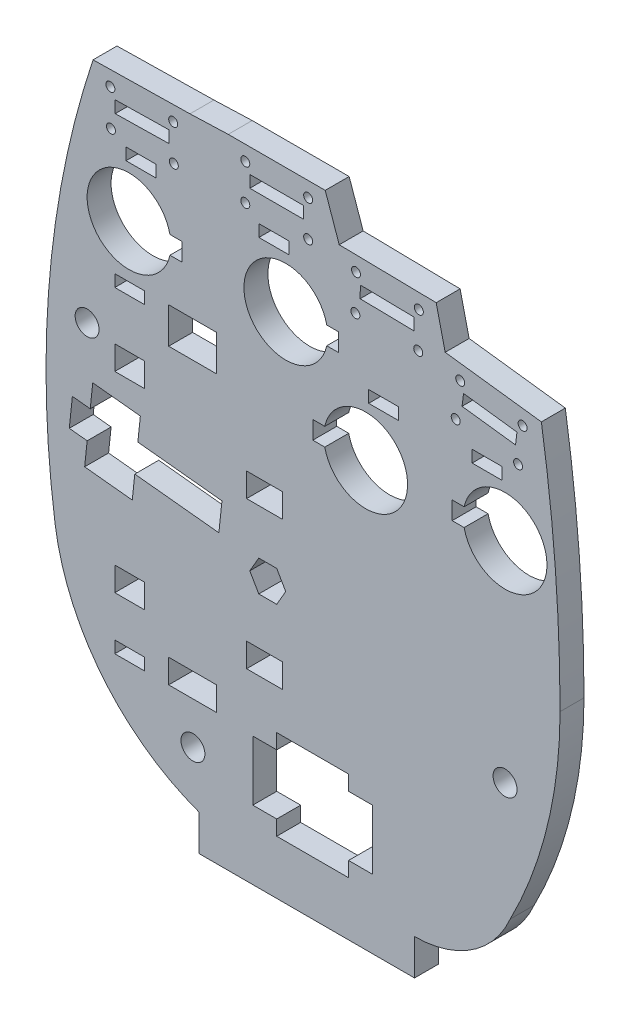
SolidWorks part; units mm, degrees
ref_plane "Front Plane" through (0, 0, 0) normal (0, 0, 1) x (1, 0, 0)
ref_plane "Top Plane" through (0, 0, 0) normal (0, 1, 0) x (1, 0, 0)
ref_plane "Right Plane" through (0, 0, 0) normal (1, 0, 0) x (0, 0, -1)
sketch "Sketch1" plane through (0, 0, 0) normal (0, 0, 1) x (1, 0, 0)
  line L0 (-4.5, 78.51) -> (-4.5, 76.51)
  line L1 (4.5, 78.51) -> (-4.5, 78.51)
  line L2 (-12.9786, -18) -> (-12.9786, -24)
  line L3 (-9.666, 24.0723) -> (-9.153, 28.9531)
  line L4 (-4.5, 76.51) -> (4.5, 76.51)
  line L5 (4.5, 76.51) -> (4.5, 78.51)
  line L6 (-34.6568, 26.6989) -> (-34.1438, 31.5798)
  line L7 (10.3588, 63.1512) -> (10.3588, 60.1512)
  line L8 (-8.1, 82.51) -> (8.1, 82.51)
  line L9 (8.3588, 63.1512) -> (10.3588, 63.1512)
  line L10 (10.4412, 75.8064) -> (26.6388, 75.5236)
  line L11 (32.6473, 57.3216) -> (37.6473, 57.3216)
  line L12 (0, 0) -> (-22.59, 0) construction
  line L13 (10.3588, 60.1512) -> (8.3588, 60.1512)
  line L14 (-17.8416, 63.1512) -> (-15.8416, 63.1512)
  line L15 (-15.8416, 63.1512) -> (-15.8416, 60.1512)
  line L16 (-15.8416, 60.1512) -> (-17.8416, 60.1512)
  line L17 (32.6473, 55.3216) -> (37.6473, 55.3216)
  line L18 (37.6473, 55.3216) -> (37.6473, 57.3216)
  line L19 (32.6473, 57.3216) -> (32.6473, 55.3216)
  line L20 (-27.0195, 78.062) -> (-18.0208, 78.2192)
  line L21 (-27.0195, 78.062) -> (-26.9845, 76.0623)
  line L22 (-10.0543, 52.8756) -> (-18.0543, 52.8756)
  line L23 (-9.153, 28.9531) -> (-23.2041, 30.43)
  line L24 (-26.9845, 76.0623) -> (-17.9858, 76.2195)
  line L25 (-24.1352, 21.571) -> (-32.0914, 22.4072)
  line L26 (-32.0914, 22.4072) -> (-31.6733, 26.3853)
  line L27 (-23.7171, 25.5491) -> (-9.666, 24.0723)
  line L28 (-17.9858, 76.2195) -> (-18.0208, 78.2192)
  line L29 (15.3631, 57.3216) -> (20.3631, 57.3216)
  line L30 (15.3631, 55.3216) -> (20.3631, 55.3216)
  line L31 (-12.9786, -24) -> (23.0214, -24)
  line L32 (20.3631, 55.3216) -> (20.3631, 57.3216)
  line L33 (23.0214, -24) -> (23.0214, -18)
  line L34 (15.3631, 57.3216) -> (15.3631, 55.3216)
  line L35 (-2.9786, 72.1512) -> (2.0214, 72.1512)
  line L36 (13.9709, 71.7441) -> (13.936, 69.7444)
  line L37 (13.936, 69.7444) -> (22.9346, 69.5874)
  line L38 (8.0257, 48.3216) -> (6.0257, 48.3216)
  line L39 (-2.9786, 70.1512) -> (2.0214, 70.1512)
  line L40 (22.9695, 71.5871) -> (13.9709, 71.7441)
  line L41 (6.0257, 48.3216) -> (6.0257, 45.3216)
  line L42 (22.9346, 69.5874) -> (22.9695, 71.5871)
  line L43 (-22.59, 0) -> (-22.59, 82.14) construction
  line L44 (2.0214, 70.1512) -> (2.0214, 72.1512)
  line L45 (18.54, 75.665) -> (18.5934, 78.7251) construction
  line L46 (-2.9786, 72.1512) -> (-2.9786, 70.1512)
  line L47 (40.1436, 63.5476) -> (31.2139, 64.6755)
  line L48 (6.0257, 45.3216) -> (8.0257, 45.3216)
  line L49 (29.3099, 45.3216) -> (31.3099, 45.3216)
  line L50 (29.3099, 48.3216) -> (29.3099, 45.3216)
  line L51 (31.3099, 48.3216) -> (29.3099, 48.3216)
  line L52 (-22.786, 34.408) -> (-30.7422, 35.2443)
  line L53 (31.2139, 64.6755) -> (30.9632, 62.6912)
  line L54 (-25.179, 72.1512) -> (-20.179, 72.1512)
  line L55 (-30.6888, 81.9985) -> (-14.4912, 82.2815)
  line L56 (44.2162, 67.065) -> (28.1438, 69.095)
  line L57 (-25.179, 70.1512) -> (-20.179, 70.1512)
  line L58 (30.9632, 62.6912) -> (39.893, 61.5633)
  line L59 (-20.179, 70.1512) -> (-20.179, 72.1512)
  line L60 (-25.179, 72.1512) -> (-25.179, 70.1512)
  line L61 (39.893, 61.5633) -> (40.1436, 63.5476)
  line L62 (-34.6568, 26.6989) -> (-31.6733, 26.3853)
  line L63 (-4, -2.5) -> (0, -2.5)
  line L64 (12, 0) -> (0, 0)
  line L65 (12, 0) -> (12, -2.5)
  line L66 (12, -15) -> (0, -15)
  line L67 (-30.7422, 35.2443) -> (-31.1603, 31.2662)
  line L68 (-23.2041, 30.43) -> (-22.786, 34.408)
  line L69 (-34.1438, 31.5798) -> (-31.1603, 31.2662)
  line L70 (-24.1352, 21.571) -> (-23.7171, 25.5491)
  line L71 (16, -7.5) -> (38.9913, -7.5) construction
  line L72 (0, -15) -> (0, -12.5)
  line L73 (-4, -12.5) -> (-4, -2.5)
  line L74 (-4, -12.5) -> (0, -12.5)
  line L75 (0, -2.5) -> (0, 0)
  line L76 (0, 0) -> (0, 82.51) construction
  line L77 (-22.0543, 52.8756) -> (-27.0543, 52.8756)
  line L78 (-10.0543, -2.1244) -> (-18.0543, -2.1244)
  line L79 (-22.0543, -2.1244) -> (-27.0543, -2.1244)
  line L80 (0, 0) -> (18.54, 0) construction
  line L81 (16, -12.5) -> (12, -12.5)
  line L82 (16, -12.5) -> (16, -2.5)
  line L83 (16, -2.5) -> (12, -2.5)
  line L84 (12, -12.5) -> (12, -15)
  line L85 (-9.4095, 26.5127) -> (6.8756, 24.8011) construction
  line L86 (0, 23.7547) -> (-3, 23.7547)
  line L87 (-3, 23.7547) -> (-4.5, 21.1566)
  line L88 (-4.5, 21.1566) -> (-3, 18.5585)
  line L89 (18.54, 0) -> (18.54, 75.665) construction
  line L90 (0, 0) -> (36.18, 0) construction
  line L91 (36.18, 0) -> (36.18, 68.08) construction
  line L92 (28.1438, 69.095) -> (26.6388, 75.5236)
  line L93 (10.4412, 75.8064) -> (8.1, 82.51)
  line L94 (-8.1, 82.51) -> (-14.4912, 82.2815)
  line L95 (-34.6568, 26.6989) -> (47.3354, 26.6989) construction
  line L96 (35.6788, 64.1115) -> (36.18, 68.08) construction
  line L97 (-3, 18.5585) -> (0, 18.5585)
  line L98 (0, 18.5585) -> (1.5, 21.1566)
  line L99 (1.5, 21.1566) -> (0, 23.7547)
  line L100 (0, 18.5585) -> (-3, 23.7547) construction
  line L101 (0, 23.7547) -> (-3, 18.5585) construction
  line L102 (38.1473, 11.8216) -> (-37.0527, 11.8216) construction
  line L103 (-27.7956, 79.5486) -> (-30.6451, 79.4989) construction
  line L104 (0.9634, 10.717) -> (0.9634, 6.717)
  line L105 (0.9634, 6.717) -> (-5.0366, 6.717)
  line L106 (-5.0366, 6.717) -> (-5.0366, 10.717)
  line L107 (-5.0366, 10.717) -> (0.9634, 10.717)
  line L108 (-5.0366, 31.3356) -> (0.9634, 31.3356)
  line L109 (-5.0366, 35.3356) -> (-5.0366, 31.3356)
  line L110 (0.9634, 35.3356) -> (-5.0366, 35.3356)
  line L111 (0.9634, 31.3356) -> (0.9634, 35.3356)
  line L112 (-30.6451, 79.4989) -> (-30.6888, 81.9985) construction
  line L113 (-17.2971, 79.732) -> (-14.4475, 79.7819) construction
  line L114 (-14.4475, 79.7819) -> (-14.4912, 82.2815) construction
  line L115 (-22.5201, 78.1406) -> (-22.59, 82.14) construction
  line L116 (5.25, 80.01) -> (8.1, 80.01) construction
  line L117 (8.1, 80.01) -> (8.1, 82.51) construction
  line L118 (-5.25, 80.01) -> (-8.1, 80.01) construction
  line L119 (-22.0543, -0.1244) -> (-27.0543, -0.1244)
  line L120 (-8.1, 80.01) -> (-8.1, 82.51) construction
  line L121 (-10.0543, 1.8756) -> (-10.0543, -2.1244)
  line L122 (30.6581, 66.2576) -> (27.8306, 66.6147) construction
  line L123 (-10.0543, 52.8756) -> (-10.0543, 46.8756)
  line L124 (-10.0543, 1.8756) -> (-18.0543, 1.8756)
  line L125 (-18.0543, 1.8756) -> (-18.0543, -2.1244)
  line L126 (27.8306, 66.6147) -> (28.1438, 69.095) construction
  line L127 (13.2472, 73.257) -> (10.3976, 73.3067) construction
  line L128 (-22.0543, -0.1244) -> (-22.0543, -2.1244)
  line L129 (-27.0543, -0.1244) -> (-27.0543, -2.1244)
  line L130 (30.6581, 66.2576) -> (29.9062, 60.3049) construction
  line L131 (-10.0543, 46.8756) -> (-18.0543, 46.8756)
  line L132 (-27.0543, 52.8756) -> (-27.0543, 50.8756)
  line L133 (-18.0543, 46.8756) -> (-18.0543, 52.8756)
  line L134 (10.4412, 75.8064) -> (10.3976, 73.3067) construction
  line L135 (-22.0543, 6.717) -> (-22.0543, 10.717)
  line L136 (-22.0543, 10.717) -> (-27.0543, 10.717)
  line L137 (-27.0543, 50.8756) -> (-22.0543, 50.8756)
  line L138 (-22.0543, 52.8756) -> (-22.0543, 50.8756)
  line L139 (-27.0543, 10.717) -> (-27.0543, 6.717)
  line L140 (-27.0543, 6.717) -> (-22.0543, 6.717)
  line L141 (-27.0543, 38.7272) -> (-22.0543, 38.7272)
  line L142 (-22.0543, 38.7272) -> (-22.0543, 42.7272)
  line L143 (-22.0543, 42.7272) -> (-27.0543, 42.7272)
  line L144 (-27.0543, 42.7272) -> (-27.0543, 38.7272)
  line L145 (23.7456, 73.0738) -> (26.5951, 73.024) construction
  line L146 (26.5951, 73.024) -> (26.6388, 75.5236) construction
  line L147 (41.0753, 64.9418) -> (43.9029, 64.5847) construction
  line L148 (41.0753, 64.9418) -> (40.3235, 58.9891) construction
  line L149 (40.3235, 58.9891) -> (43.151, 58.632) construction
  line L150 (43.151, 58.632) -> (43.9029, 64.5847) construction
  line L151 (23.7456, 73.0738) -> (23.6409, 67.0747) construction
  line L152 (13.2472, 73.257) -> (13.1425, 67.2579) construction
  line L153 (-17.2971, 79.732) -> (-17.1923, 73.733) construction
  line L154 (-27.7956, 79.5486) -> (-27.6908, 73.5496) construction
  line L155 (38.1473, 46.8216) -> (38.1473, 11.8216) construction
  arc A0 (-37.0527, 11.8216) -> (-30.6888, 81.9985) centre (116.3395, 33.2885) cw
  circle A1 centre (-1.5, 21.1566) radius 4.5 construction
  arc A2 (8.3588, 63.1512) -> (8.3588, 60.1512) centre (1.5214, 61.6512) ccw
  arc A3 (8.0257, 45.3216) -> (8.0257, 48.3216) centre (14.8631, 46.8216) ccw
  arc A4 (-17.8416, 63.1512) -> (-17.8416, 60.1512) centre (-24.679, 61.6512) ccw
  arc A5 (31.3099, 45.3216) -> (31.3099, 48.3216) centre (38.1473, 46.8216) ccw
  arc A6 (23.0214, -18) -> (38.9913, -7.5) centre (23.0214, -0.6053) ccw
  arc A7 (47.3354, 26.6989) -> (38.9913, -7.5) centre (-26.9196, 26.6989) cw
  arc A8 (-37.0527, 11.8216) -> (-12.9786, -18) centre (-0.147, 16.9865) ccw
  arc A9 (47.3354, 26.6989) -> (44.2162, 67.065) centre (-215.4084, 26.6989) ccw
  circle A11 centre (38.1473, 11.8216) radius 2
  circle A12 centre (-14, -9.1244) radius 2
  circle A18 centre (-5.25, 80.01) radius 0.75
  circle A22 centre (-31.6815, 43.4564) radius 2
  circle A49 centre (5.25, 80.01) radius 0.75
  circle A50 centre (5.25, 74.01) radius 0.75
  circle A51 centre (-5.25, 74.01) radius 0.75
  circle A52 centre (-27.7956, 79.5486) radius 0.75
  circle A53 centre (-17.2971, 79.732) radius 0.75
  circle A54 centre (-27.6908, 73.5496) radius 0.75
  circle A55 centre (-17.1923, 73.733) radius 0.75
  circle A56 centre (23.6409, 67.0747) radius 0.75
  circle A57 centre (13.1425, 67.2579) radius 0.75
  circle A58 centre (23.7456, 73.0738) radius 0.75
  circle A59 centre (13.2472, 73.257) radius 0.75
  circle A60 centre (29.9062, 60.3049) radius 0.7496
  circle A61 centre (41.0753, 64.9418) radius 0.7496
  circle A62 centre (30.6581, 66.2576) radius 0.7496
  circle A63 centre (40.3235, 58.9891) radius 0.7496
  dimension "D1" = 4
  dimension "D2" = 1.5
  dimension "D11" = 1.5214
  dimension "D12" = 2.0214
  dimension "D16" = 6.0257
  dimension "D17" = 4
  dimension "D18" = 8.3588
  dimension "D19" = 22.59
  dimension "D22" = 4
  dimension "D23" = 18.54
  dimension "D24" = 75.665
  dimension "D25" = 12
  dimension "D35" = 4
  dimension "D36" = 16.2
  dimension "D37" = 2
  dimension "D38" = 29.3099
  dimension "D39" = 2.85
  dimension "D40" = 46.8216
  dimension "D43" = 2.85
  dimension "D44" = 24.679
  dimension "D45" = 9
  dimension "D46" = 0.7292
  dimension "D47" = 4.9078
  dimension "D49" = 5.0366
  dimension "D51" = 9.666
  dimension "D55" = 24
  dimension "D56" = 15.8416
  dimension "D13" = 4
  dimension "D58" = 2.5
  dimension "D59" = 18.0543
  dimension "D60" = 8.1
  dimension "D61" = 6
  dimension "D63" = 22.0543
  dimension "D64" = 2.5
  dimension "D65" = 2.85
  dimension "D52" = 10.0543
  dimension "D48" = 25.1285
  dimension "D53" = 12.9786
  dimension "D57" = 4
  dimension "D69" = 6
  dimension "D70" = 2.5
  dimension "D71" = 1.8756
  dimension "D79" = 43.4564
  dimension "D82" = 55.3216
  dimension "D67" = 2.5
  dimension "D68" = 31.6815
  dimension "D5" = 7
  dimension "D29" = 2.5
  dimension "D83" = 8.1
  dimension "D85" = 2
  dimension "D10" = 0.9634
  dimension "D14" = 82.51
  dimension "D15" = 3
  dimension "D20" = 10
  dimension "D21" = 82.14
  dimension "D26" = 15.3631
  dimension "D27" = 2.5
  dimension "D28" = 0
  dimension "D30" = 20.3631
  dimension "D31" = 36.18
  dimension "D32" = 68.08
  dimension "D33" = 23.0214
  dimension "D34" = 6
  dimension "D41" = 14.8631
  dimension "D42" = 32.6473
  dimension "D50" = 9.153
  dimension "D54" = 14
  dimension "D62" = 20.179
  dimension "D66" = 2.85
  dimension "D72" = 6.717
  dimension "D73" = 9.0001
  dimension "D74" = 9.0007
  dimension "D75" = 35
  dimension "D76" = 21.571
  dimension "D77" = 31.3356
  dimension "D78" = 6
  dimension "D80" = 45.3216
  dimension "D81" = 46.8756
  dimension "D84" = 60.1512
  dimension "D86" = 70.1512
  dimension "D93" = 9.1244
extrude "Boss-Extrude1" add sketch "Sketch1" along normal blind 4
equation "\"D14@Sketch1\"= \"HL@parametersSketch@prostheticParameters.SLDPRT\" * 0.446'Mioddle Base Frame "
equation "\"D19@Sketch1\"= \"HB@parametersSketch@prostheticParameters.SLDPRT\" * 0.251'Index Base Frame X"
equation "\"D21@Sketch1\"= \"HL@parametersSketch@prostheticParameters.SLDPRT\" * 0.444'Index Base Frame Y"
equation "\"D23@Sketch1\"= \"HB@parametersSketch@prostheticParameters.SLDPRT\" * 0.206'Ring Base Frame X"
equation "\"D24@Sketch1\"= \"HL@parametersSketch@prostheticParameters.SLDPRT\" * 0.409'Ring Base Frame Y"
equation "\"D31@Sketch1\"= \"HB@parametersSketch@prostheticParameters.SLDPRT\" * 0.402'Pinky Base Frame X"
equation "\"D32@Sketch1\"= \"HL@parametersSketch@prostheticParameters.SLDPRT\" * 0.368'Pinky Base Frame Y"
equation "\"D36@Sketch1\"= \"fingerWidth@parametersSketch@prostheticParameters.SLDPRT\"'Fingers Width"
equation "\"D76@Sketch1\"= \"HL@parametersSketch@prostheticParameters.SLDPRT\" * 0.1166'Hole Thumb Y"
equation "\"D51@Sketch1\"= \"HB@parametersSketch@prostheticParameters.SLDPRT\" * 0.1074'Hole Thumb X1"
equation "\"D50@Sketch1\" = \"HB@parametersSketch@prostheticParameters.SLDPRT\" * 0.1017'Hole Thumb X2"
equation "\"D73@Sketch1\"= \"fingerWidth@parametersSketch@prostheticParameters.SLDPRT\" * 0.55556"
equation "\"D74@Sketch1\"= \"fingerWidth@parametersSketch@prostheticParameters.SLDPRT\" * 0.5556"
equation "\"D60@Sketch1\"= \"fingerWidth@parametersSketch@prostheticParameters.SLDPRT\" / 2"
equation "\"D83@Sketch1\"= \"fingerWidth@parametersSketch@prostheticParameters.SLDPRT\" / 2"
